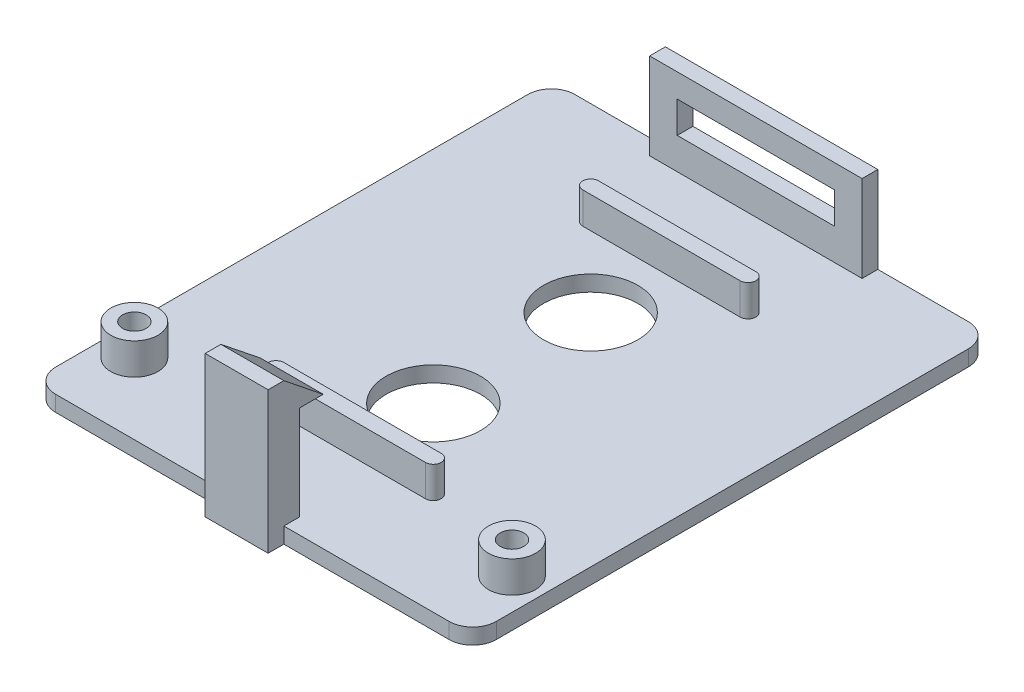
SolidWorks part; units mm, degrees
ref_plane "Front Plane" through (0, 0, 0) normal (0, 0, 1) x (1, 0, 0)
ref_plane "Top Plane" through (0, 0, 0) normal (0, 1, 0) x (1, 0, 0)
ref_plane "Right Plane" through (0, 0, 0) normal (1, 0, 0) x (0, 0, -1)
sketch "Base" plane through (0, 0, 0) normal (0, 1, 0) x (1, 0, 0)
  line L0 (-5, -10) -> (5, -10) construction
  line L1 (12.5, 16.5) -> (-12.5, 16.5)
  line L2 (14, 15) -> (14, -15)
  line L3 (12.5, -16.5) -> (-12.5, -16.5)
  line L4 (-14, 15) -> (-14, -15)
  line L6 (2, -15.5) -> (-2, -15.5)
  line L7 (2, -15.5) -> (2, -16.5)
  line L8 (2, -16.5) -> (-2, -16.5)
  line L9 (-2, -15.5) -> (-2, -16.5)
  line L10 (2, -15.5) -> (-2, -16.5) construction
  line L11 (-5, -9.5) -> (5, -9.5)
  line L12 (-5, -10.5) -> (5, -10.5)
  line L13 (-5, 10) -> (5, 10) construction
  line L14 (-6.75, 16.5) -> (6.75, 16.5)
  line L15 (-6.75, 16.5) -> (-6.75, 15.5)
  line L16 (-6.75, 15.5) -> (6.75, 15.5)
  line L17 (6.75, 16.5) -> (6.75, 15.5)
  line L18 (-5, 10.5) -> (5, 10.5)
  line L19 (-5, 9.5) -> (5, 9.5)
  line L20 (2, -16.5) -> (-2, -15.5) construction
  line L21 (2, -16.5) -> (-2, -16.5)
  line L22 (2, -16.5) -> (2, -17.5)
  line L23 (2, -17.5) -> (-2, -17.5)
  line L24 (-2, -16.5) -> (-2, -17.5)
  line L25 (2, -16.5) -> (-2, -17.5) construction
  line L26 (2, -17.5) -> (-2, -16.5) construction
  arc A0 (-12.5, 16.5) -> (-14, 15) centre (-12.5, 15) ccw
  arc A1 (14, 15) -> (12.5, 16.5) centre (12.5, 15) ccw
  arc A2 (-12.5, -16.5) -> (-14, -15) centre (-12.5, -15) cw
  arc A3 (14, -15) -> (12.5, -16.5) centre (12.5, -15) cw
  circle A4 centre (-12, -12) radius 1.5
  circle A5 centre (-12, -12) radius 0.75
  circle A6 centre (12, -12) radius 1.5
  circle A7 centre (12, -12) radius 0.75
  arc A8 (-5, -9.5) -> (-5, -10.5) centre (-5, -10) ccw
  arc A9 (5, -10.5) -> (5, -9.5) centre (5, -10) ccw
  arc A10 (-5, 10.5) -> (-5, 9.5) centre (-5, 10) ccw
  arc A11 (5, 9.5) -> (5, 10.5) centre (5, 10) ccw
  circle A12 centre (0, 5) radius 3
  circle A13 centre (0, -5) radius 3
  point P4 (-12, -12)
  point P5 (0, -16)
  point P21 (12, -12)
  point P29 (0, -17)
  point P33 (0, -10)
  point P42 (0, 10)
sketch "PCB holder" plane through (0, 0, 0) normal (0, 1, 0) x (1, 0, 0)
  line L0 (-10, -10.5) -> (-12, -10.5)
  line L1 (9, 15.5) -> (-9, 15.5)
  line L2 (10, 14.5) -> (10, -14.5)
  line L3 (9, -15.5) -> (-9, -15.5)
  line L4 (-10, 14.5) -> (-10, -14.5)
  line L5 (-12, -13.5) -> (-10, -13.5)
  line L6 (12, -10.5) -> (10, -10.5)
  line L7 (8.75, 14.75) -> (-8.75, 14.75)
  line L8 (9.25, 14.25) -> (9.25, -14.25)
  line L9 (8.75, -14.75) -> (-8.75, -14.75)
  line L10 (-9.25, 14.25) -> (-9.25, -14.25)
  line L11 (12, -13.5) -> (10, -13.5)
  line L13 (-4.75, 15.5) -> (4.75, 15.5)
  line L14 (-4.75, 15.5) -> (-4.75, 16.75)
  line L15 (-4.75, 16.75) -> (4.75, 16.75)
  line L16 (4.75, 15.5) -> (4.75, 16.75)
  arc A0 (-9.25, 14.25) -> (-8.75, 14.75) centre (-8.75, 14.25) cw
  arc A1 (9.25, 14.25) -> (8.75, 14.75) centre (8.75, 14.25) ccw
  arc A2 (8.75, -14.75) -> (9.25, -14.25) centre (8.75, -14.25) ccw
  arc A3 (-9.25, -14.25) -> (-8.75, -14.75) centre (-8.75, -14.25) ccw
  arc A4 (-9, 15.5) -> (-10, 14.5) centre (-9, 14.5) ccw
  arc A5 (9, 15.5) -> (10, 14.5) centre (9, 14.5) cw
  arc A6 (-10, -14.5) -> (-9, -15.5) centre (-9, -14.5) ccw
  arc A7 (10, -14.5) -> (9, -15.5) centre (9, -14.5) cw
  arc A8 (-12, -10.5) -> (-12, -13.5) centre (-12, -12) ccw
  arc A9 (12, -10.5) -> (12, -13.5) centre (12, -12) cw
  circle A10 centre (-12, -12) radius 0.75
  circle A11 centre (12, -12) radius 0.75
  circle A12 centre (0, 5) radius 3
  circle A13 centre (0, -5) radius 3
  point P0 (0, 0)
  point P1 (0, 0)
  point P7 (0, 0)
  line B0 (-8.5, 14.5) -> (8.5, 14.5) construction
  line B1 (-9, 14) -> (-9, -14) construction
  line B2 (-8.5, -14.5) -> (8.5, -14.5) construction
  line B3 (9, 14) -> (9, -14) construction
  arc B4 (-9, 14) -> (-8.5, 14.5) centre (-8.5, 14) cw construction
  arc B5 (9, 14) -> (8.5, 14.5) centre (8.5, 14) ccw construction
  arc B6 (8.5, -14.5) -> (9, -14) centre (8.5, -14) ccw construction
  arc B7 (-9, -14) -> (-8.5, -14.5) centre (-8.5, -14) ccw construction
sketch_block_instance "Block2-1"
sketch_block "Block2"
extrude "Boss-Extrude5" add sketch "Base<4>" along normal blind 3 contours A4 A5 | A6 A7 region at (-13.4576, 0, 12) region at (10.5424, 0, 12)
sketch "Base<4>" plane through (0, 0, 0) normal (0, 1, 0) x (1, 0, 0) same geometry as "Base"
extrude "Boss-Extrude7" add sketch "Base" along normal blind 6.5 contours L17 L1 L15 L16 region at (0, 0, -16)
extrude "Boss-Extrude8" add sketch "Base<7>" along normal blind 1 contours A3 L2 A1 L1 L17 L16 L15 A0 L4 A2 L3 A13 A12 A11 L19 A10 L18 A9 L12 A8 L11 A6 A4 | L19 A11 L18 A10 | L12 A9 L11 A8 region at (0, 0, -0.0217)
sketch "Base<7>" plane through (0, 0, 0) normal (0, 1, 0) x (1, 0, 0) same geometry as "Base"
extrude "Boss-Extrude9" add sketch "Base<8>" along normal blind 3 contours L19 A11 L18 A10 | L11 A9 L12 A8
sketch "Base<8>" plane through (0, 0, 0) normal (0, 1, 0) x (1, 0, 0) same geometry as "Base"
sketch "slit" plane through (0, 0, -15.5) normal (0, 0, 1) x (1, 0, 0)
  line L1 (-5, 5) -> (5, 5)
  line L2 (-5, 5) -> (-5, 3)
  line L3 (-5, 3) -> (5, 3)
  line L4 (5, 5) -> (5, 3)
extrude "Cut-Extrude2" cut sketch "slit" against normal blind 6.5
extrude "Boss-Extrude12" add sketch "Base<13>" along normal blind 9 contours L6 L9 L3 L7 region at (0, 0, 16)
sketch "Base<13>" plane through (0, 0, 0) normal (0, 1, 0) x (1, 0, 0) same geometry as "Base"
sketch "Sketch3" plane through (2, 0, 0) normal (1, 0, 0) x (0, 0, -1)
  line L0 (-14, 7) -> (-15.5, 9)
  line L2 (-15.5, 9) -> (-15.5, 7)
  line L3 (-15.5, 7) -> (-14, 7)
  line L5 (-15.5, 7) -> (-14, 7)
  line M3 (-15.5, 1) -> (-15.5, 9)
extrude "Boss-Extrude13" add sketch "Sketch3" against normal blind 4 contours L3 L0 M3 region at (2, 7.6667, 15)
sketch "Sketch4" plane through (2, 0, 0) normal (1, 0, 0) x (0, 0, -1)
  line L0 (-14, 7) -> (-16.5, 9)
  line L1 (-16.5, 9) -> (-13.8372, 9)
  line L2 (-13.8372, 9) -> (-14, 7)
extrude "Cut-Extrude3" cut sketch "Sketch4" against normal blind 4
extrude "Boss-Extrude14" add sketch "Base<14>" along normal blind 9 contours L3 L24 L23 L22 region at (0, 0, 17)
sketch "Base<14>" plane through (0, 0, 0) normal (0, 1, 0) x (1, 0, 0) same geometry as "Base"
